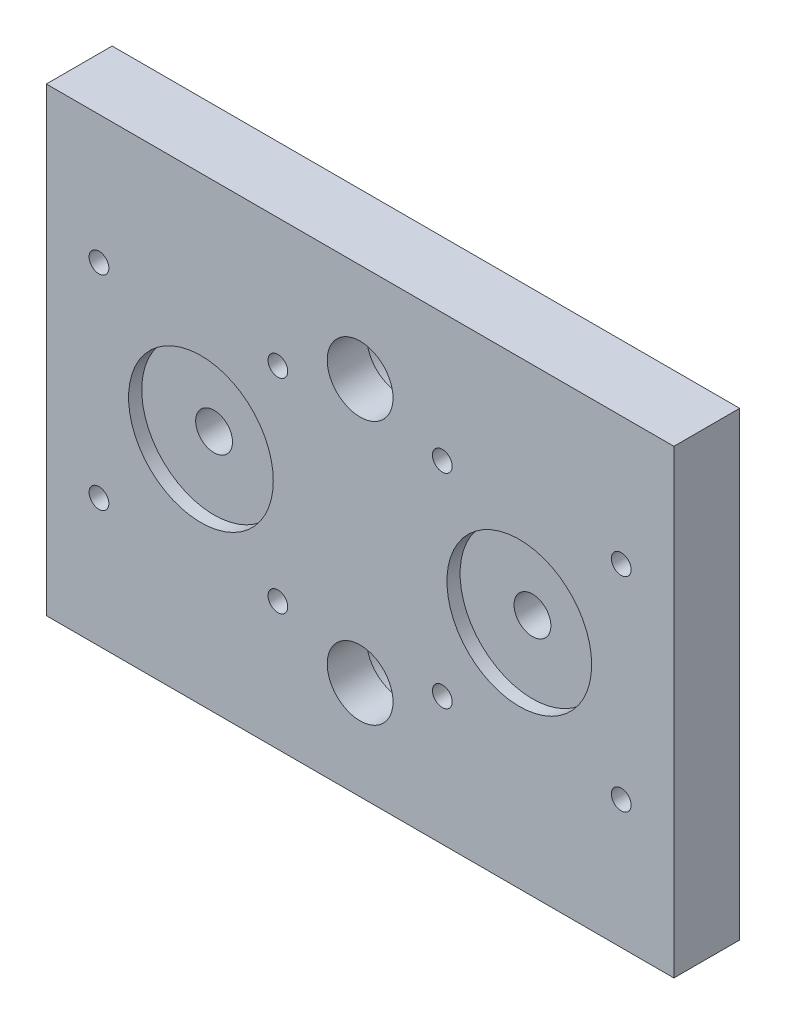
SolidWorks part; units mm, degrees
ref_plane "Front Plane" through (0, 0, 0) normal (0, 0, 1) x (1, 0, 0)
ref_plane "Top Plane" through (0, 0, 0) normal (0, 1, 0) x (1, 0, 0)
ref_plane "Right Plane" through (0, 0, 0) normal (1, 0, 0) x (0, 0, -1)
sketch "Sketch1" plane through (0, 0, 0) normal (0, 0, 1) x (1, 0, 0)
  line L0 (0, 0) -> (0, 40) construction
  line L2 (12.5, -15) -> (-12.5, -15)
  line L3 (12.5, -15) -> (12.5, 55)
  line L4 (12.5, 55) -> (-12.5, 55)
  line L5 (-12.5, -15) -> (-12.5, 55)
  line L6 (12.5, -15) -> (-12.5, 55) construction
  line L7 (12.5, 55) -> (-12.5, -15) construction
  circle A0 centre (0, 40) radius 7.9375
  circle A1 centre (0, 0) radius 7.9375
  point P5 (0, 20)
  dimension "D2" = 15.875
  dimension "D1" = 40
  dimension "D3" = 70
  dimension "D4" = 25
extrude "Boss-Extrude1" add sketch "Sketch1" along normal blind 10
sketch "Sketch2" plane through (0, 0, 10) normal (0, 0, 1) x (1, 0, 0)
  line L0 (12.5, 55) -> (-12.5, 55) construction
  line L1 (-47.7, 55) -> (-8.2, 55)
  line L3 (-47.7, -15) -> (-8.2, -15)
  line L4 (-8.2, 55) -> (-8.2, 36.9142)
  line L5 (-39.7, 35.5) -> (-8.7, 4.5) construction
  line L6 (-39.7, 4.5) -> (-8.7, 35.5) construction
  line L7 (-12.5, -15) -> (12.5, -15) construction
  line L8 (-8.2, 34.0858) -> (-8.2, 5.9142)
  line L9 (0, 55) -> (0, -15) construction
  line L10 (-8.7, 4.5) -> (-39.7, 4.5) construction
  line L11 (-8.7, 4.5) -> (-8.7, 35.5) construction
  line L12 (-8.7, 35.5) -> (-39.7, 35.5) construction
  line L13 (-39.7, 4.5) -> (-39.7, 35.5) construction
  line L14 (-8.7, 4.5) -> (-39.7, 35.5) construction
  line L15 (-8.7, 35.5) -> (-39.7, 4.5) construction
  line L16 (8.7, 35.5) -> (39.7, 4.5) construction
  line L17 (8.7, 4.5) -> (39.7, 35.5) construction
  line L18 (39.7, 4.5) -> (39.7, 35.5) construction
  line L19 (8.7, 35.5) -> (39.7, 35.5) construction
  line L20 (8.7, 4.5) -> (8.7, 35.5) construction
  line L21 (8.7, 4.5) -> (39.7, 4.5) construction
  line L22 (39.7, 4.5) -> (8.7, 35.5) construction
  line L23 (39.7, 35.5) -> (8.7, 4.5) construction
  line L24 (8.2, 55) -> (8.2, 36.9142)
  line L25 (47.7, -15) -> (8.2, -15)
  line L27 (47.7, 55) -> (8.2, 55)
  line L28 (-47.7, 55) -> (-47.7, -15)
  line L29 (47.7, 55) -> (47.7, -15)
  line L31 (-8.2, 3.0858) -> (-8.2, -15)
  line L32 (8.2, 3.0858) -> (8.2, -15)
  line L33 (8.2, 34.0858) -> (8.2, 5.9142)
  circle A0 centre (-39.7, 35.5) radius 1.5
  arc A1 (-8.2, 36.9142) -> (-8.2, 34.0858) centre (-8.7, 35.5) ccw
  arc A2 (-8.2, 5.9142) -> (-8.2, 3.0858) centre (-8.7, 4.5) ccw
  circle A3 centre (-39.7, 4.5) radius 1.5
  circle A4 centre (39.7, 4.5) radius 1.5
  arc A5 (8.2, 5.9142) -> (8.2, 3.0858) centre (8.7, 4.5) cw
  arc A6 (8.2, 36.9142) -> (8.2, 34.0858) centre (8.7, 35.5) cw
  circle A7 centre (39.7, 35.5) radius 1.5
  circle A8 centre (-24.2, 20) radius 2.8
  circle A9 centre (24.2, 20) radius 2.8
  point P0 (-24.2, 20)
  point P11 (-24.2, 20)
  point P34 (24.2, 20)
  dimension "D2" = 3
  dimension "D3" = 5.6
  dimension "D1" = 31
  dimension "D4" = 0.5
  dimension "D5" = 8
  dimension "D6" = 8.2
extrude "Boss-Extrude2" add sketch "Sketch2" against normal up to surface (10 mm away) up to face at (0, 20, 0)
sketch "Sketch6" plane through (0, 0, 10) normal (0, 0, 1) x (1, 0, 0)
  circle A0 centre (-12.5, 35.5) radius 1.5
  circle A1 centre (12.5, 35.5) radius 1.5
  circle A2 centre (-12.5, 4.5) radius 1.5
  circle A3 centre (12.5, 4.5) radius 1.5
  circle A5 centre (-39.7, 35.5) radius 1.5 construction
extrude "Cut-Extrude3" cut sketch "Sketch6" against normal up to surface (10 mm away) up to face at (0, 20, 0)
sketch "Sketch3" plane through (0, 0, 10) normal (0, 0, 1) x (1, 0, 0)
  circle A0 centre (0, 40) radius 7.9375
  circle A1 centre (0, 0) radius 7.9375
  circle A2 centre (0, 40) radius 7.9375 construction
  circle A3 centre (0, 40) radius 5
  circle A4 centre (0, 0) radius 5
  circle A8 centre (0, 0) radius 7.9375 construction
  point P2 (0, 0)
  point P10 (0, 3.4239)
  point P12 (0.2927, 41.4803)
  dimension "D1" = 10
extrude "Boss-Extrude3" add sketch "Sketch3" against normal blind 6.0216
sketch "Sketch4" plane through (0, 0, 10) normal (0, 0, 1) x (1, 0, 0)
  circle A0 centre (-24.2, 20) radius 11
  circle A1 centre (24.2, 20) radius 11
  dimension "D1" = 22
extrude "Cut-Extrude1" cut sketch "Sketch4" against normal blind 2
sketch "Sketch5" plane through (0, 0, 0) normal (0, 0, -1) x (-1, 0, 0)
  circle A0 centre (-39.7, 35.5) radius 2.75
  circle A1 centre (-12.5, 35.5) radius 2.75
  circle A2 centre (-39.7, 4.5) radius 2.75
  circle A3 centre (-12.5, 4.5) radius 2.75
  circle A4 centre (12.5, 35.5) radius 2.75
  circle A5 centre (39.7, 35.5) radius 2.75
  circle A6 centre (12.5, 4.5) radius 2.75
  circle A7 centre (39.7, 4.5) radius 2.75
  circle A9 centre (12.5, 4.5) radius 1.5 construction
  circle A10 centre (-12.5, 4.5) radius 1.5 construction
  circle A11 centre (-12.5, 35.5) radius 1.5 construction
  circle A12 centre (12.5, 35.5) radius 1.5 construction
  dimension "D1" = 5.5
extrude "Cut-Extrude2" cut sketch "Sketch5" against normal blind 3.1
sketch "Sketch11" plane through (0, 0, 0) normal (0, 0, -1) x (-1, 0, 0)
  circle A0 centre (-24.2, 20) radius 10.2
  circle A1 centre (24.2, 20) radius 10.2
  dimension "D1" = 20.4
extrude "Cut-Extrude6" cut sketch "Sketch11" against normal blind 2
